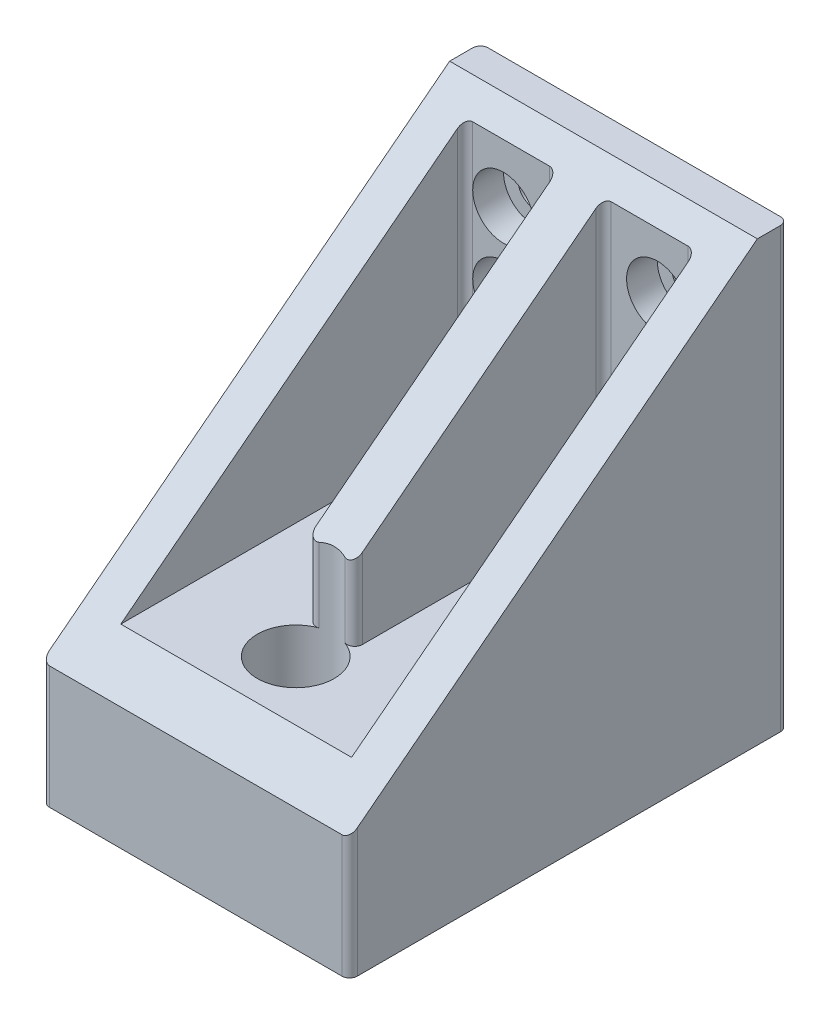
SolidWorks part; units mm, degrees
ref_plane "Plan de face" through (0, 0, 0) normal (0, 0, 1) x (1, 0, 0)
ref_plane "Plan de dessus" through (0, 0, 0) normal (0, 1, 0) x (1, 0, 0)
ref_plane "Plan de droite" through (0, 0, 0) normal (1, 0, 0) x (0, 0, -1)
sketch "Esquisse1" plane through (0, 0, 0) normal (1, 0, 0) x (0, 0, -1)
  line L0 (0, 0) -> (-57, 0)
  line L1 (-57, 0) -> (-57, 15.925)
  line L2 (-57, 15.925) -> (-4, 57)
  line L3 (-4, 57) -> (0, 57)
  line L4 (0, 57) -> (0, 0)
  line L5 (-44, 0) -> (-44, 26) construction
  dimension "D1" = 44
  dimension "D2" = 13
  dimension "D3" = 4
  dimension "D4" = 26
extrude "Boss.-Extru.1" add sketch "Esquisse1" along normal blind 40
sketch "Esquisse2" plane through (0, 0, 0) normal (0, -1, 0) x (1, 0, 0)
  line L0 (20, 57) -> (20, 0) construction
  line L1 (40, 57) -> (0, 57) construction
  line L2 (40, 0) -> (0, 0) construction
  circle A0 centre (20, 44) radius 5
  dimension "D1" = 10
  dimension "D2" = 44
extrude "Enlèv. mat.-Extru.1" cut sketch "Esquisse2" against normal blind 40
sketch "Esquisse3" plane through (0, 0, 0) normal (0, 0, -1) x (-1, 0, 0)
  line L0 (-20, 57) -> (-20, 0) construction
  line L1 (-40, 57) -> (0, 57) construction
  line L2 (-40, 0) -> (0, 0) construction
  line L3 (-30, 47) -> (-10, 47) construction
  line L4 (-30, 37) -> (-10, 37) construction
  line L5 (-30, 27) -> (-10, 27) construction
  circle A0 centre (-30, 47) radius 2.1
  circle A1 centre (-10, 47) radius 2.1
  circle A2 centre (-30, 37) radius 2.1
  circle A3 centre (-10, 37) radius 2.1
  circle A4 centre (-30, 27) radius 2.1
  circle A5 centre (-10, 27) radius 2.1
  dimension "D1" = 4.2
  dimension "D2" = 20
  dimension "D3" = 10
  dimension "D4" = 3
extrude "Enlèv. mat.-Extru.2" cut sketch "Esquisse3" against normal through all
sketch "Esquisse4" plane through (0, 0, 0) normal (0, 0, -1) x (-1, 0, 0)
  line L0 (-40, 0) -> (0, 0) construction
  line L1 (-32.9, 0) -> (-27.1, 0)
  line L2 (-32.9, 0) -> (-32.9, 20)
  line L3 (-32.9, 20) -> (-27.1, 20)
  line L4 (-27.1, 0) -> (-27.1, 20)
  line L5 (-20, 57) -> (-20, 0) construction
  line L6 (-40, 57) -> (0, 57) construction
  line L7 (-12.9, 0) -> (-12.9, 20)
  line L8 (-7.1, 20) -> (-12.9, 20)
  line L9 (-7.1, 0) -> (-7.1, 20)
  line L10 (-7.1, 0) -> (-12.9, 0)
  point P14 (-30, 20)
  point P15 (-10, 20)
  dimension "D1" = 5.8
  dimension "D2" = 20
  dimension "D3" = 20
extrude "Boss.-Extru.2" add sketch "Esquisse4" along normal blind 2
sketch "Esquisse5" plane through (0, 0, 57) normal (0, 0, 1) x (1, 0, 0)
  circle A0 centre (10, 47) radius 4
  circle A1 centre (30, 47) radius 4
  circle A2 centre (10, 37) radius 4
  circle A3 centre (30, 37) radius 4
  circle A4 centre (10, 27) radius 4
  circle A5 centre (30, 27) radius 4
  dimension "D1" = 8
  dimension "D2" = 3
extrude "Enlèv. mat.-Extru.3" cut sketch "Esquisse5" against normal blind 54
sketch "Esquisse6" plane through (0, 0, 57) normal (0, 0, 1) x (1, 0, 0)
  line L0 (40, 57) -> (0, 57) construction
  line L1 (5, 57) -> (17, 57)
  line L2 (5, 57) -> (5, 20)
  line L3 (5, 20) -> (17, 20)
  line L4 (35, 57) -> (35, 20)
  line L5 (40, 0) -> (0, 0) construction
  line L6 (0, 57) -> (0, 15.925) construction
  line L7 (40, 57) -> (40, 15.925) construction
  line L8 (23, 57) -> (35, 57)
  line L10 (17, 57) -> (17, 20)
  line L12 (23, 57) -> (23, 20)
  line L13 (23, 20) -> (35, 20)
  dimension "D1" = 20
  dimension "D2" = 5
  dimension "D3" = 5
  dimension "D4" = 12
  dimension "D5" = 12
extrude "Enlèv. mat.-Extru.4" cut sketch "Esquisse6" against normal blind 50
sketch "Esquisse7" plane through (0, 20, 0) normal (0, 1, 0) x (1, 0, 0)
  line L1 (17, -51.7419) -> (23, -51.7419)
  line L2 (17, -51.7419) -> (17, -48)
  line L3 (17, -48) -> (23, -48)
  line L4 (23, -51.7419) -> (23, -48)
extrude "Enlèv. mat.-Extru.5" cut sketch "Esquisse7" along normal blind 50
fillet "Congé1" radius 1 10 edges at (35, 37.3375, 7) (23, 37.3375, 7) (17, 37.3375, 7) (5, 37.3375, 7) (0, 28.5, 0) (40, 28.5, 0) (40, 7.9625, 57) (0, 7.9625, 57) (23, 24.55, 40) (17, 24.55, 40)
fillet "Congé2" radius 0.5 4 edges at (7.1, 10, -2) (12.9, 10, -2) (27.1, 10, -2) (32.9, 10, -2)
